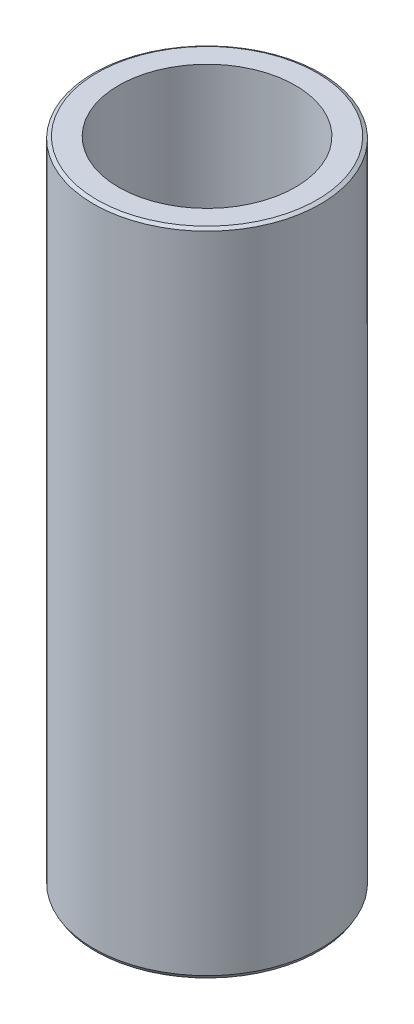
SolidWorks part; units mm, degrees
ref_plane "Front Plane" through (0, 0, 0) normal (0, 0, 1) x (1, 0, 0)
ref_plane "Top Plane" through (0, 0, 0) normal (0, 1, 0) x (1, 0, 0)
ref_plane "Right Plane" through (0, 0, 0) normal (1, 0, 0) x (0, 0, -1)
sketch "Sketch1" plane through (0, 0, 0) normal (0, 1, 0) x (1, 0, 0)
  circle A0 centre (0, 0) radius 17.5
  dimension "SHAFT_OD" = 35
extrude "Boss-Extrude1" add sketch "Sketch1" along normal blind 100.2676
sketch "Sketch2" plane through (0, 0, 0) normal (0, 1, 0) x (1, 0, 0)
  circle A0 centre (0, 0) radius 13.6219
  dimension "BORE_D" = 27.2438
extrude "Cut-Extrude1" cut sketch "Sketch2" along normal through all
chamfer "Chamfer1" distance 0.3027 angle 60 2 edges at (0, 100.2676, 17.5) (0, 0, 17.5) first distance on face at (0, 100.2676, 17.5) first distance on face at (0, 0, 13.6219)
